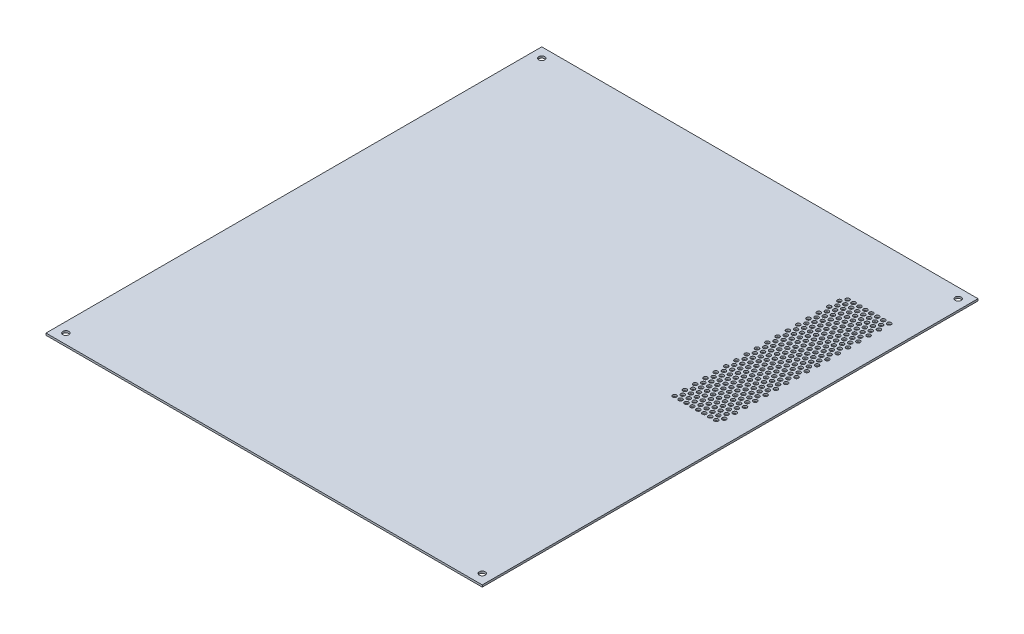
SolidWorks part; units mm, degrees
ref_plane "Front Plane" through (0, 0, 0) normal (0, 0, 1) x (1, 0, 0)
ref_plane "Top Plane" through (0, 0, 0) normal (0, 1, 0) x (1, 0, 0)
ref_plane "Right Plane" through (0, 0, 0) normal (1, 0, 0) x (0, 0, -1)
sketch "Sketch1" plane through (0, 0, 0) normal (0, 1, 0) x (1, 0, 0)
  line L0 (20, 20) -> (20, 480) construction
  line L1 (0, 0) -> (440, 0)
  line L2 (0, 0) -> (0, 500)
  line L3 (0, 500) -> (440, 500)
  line L4 (440, 0) -> (440, 500)
  line L5 (20, 480) -> (420, 480) construction
  line L6 (420, 20) -> (420, 480) construction
  line L7 (20, 20) -> (420, 20) construction
  line L9 (420, 440) -> (370, 440) construction
  line L10 (420, 440) -> (420, 260) construction
  line L11 (420, 260) -> (370, 260) construction
  line L12 (370, 440) -> (370, 260) construction
  circle A0 centre (372, 262) radius 2
  circle A1 centre (375, 267.1962) radius 2
  circle A2 centre (381, 267.1962) radius 2
  circle A3 centre (378, 262) radius 2
  circle A4 centre (387, 267.1962) radius 2
  circle A5 centre (384, 262) radius 2
  circle A6 centre (393, 267.1962) radius 2
  circle A7 centre (390, 262) radius 2
  circle A8 centre (399, 267.1962) radius 2
  circle A9 centre (396, 262) radius 2
  circle A10 centre (405, 267.1962) radius 2
  circle A11 centre (402, 262) radius 2
  circle A12 centre (411, 267.1962) radius 2
  circle A13 centre (408, 262) radius 2
  circle A14 centre (417, 267.1962) radius 2
  circle A15 centre (414, 262) radius 2
  circle A16 centre (381, 277.5862) radius 2
  circle A17 centre (378, 272.39) radius 2
  circle A18 centre (387, 277.5862) radius 2
  circle A19 centre (384, 272.39) radius 2
  circle A20 centre (393, 277.5862) radius 2
  circle A21 centre (390, 272.39) radius 2
  circle A22 centre (399, 277.5862) radius 2
  circle A23 centre (396, 272.39) radius 2
  circle A24 centre (405, 277.5862) radius 2
  circle A25 centre (402, 272.39) radius 2
  circle A26 centre (411, 277.5862) radius 2
  circle A27 centre (408, 272.39) radius 2
  circle A28 centre (417, 277.5862) radius 2
  circle A29 centre (414, 272.39) radius 2
  circle A30 centre (381, 287.9762) radius 2
  circle A31 centre (378, 282.78) radius 2
  circle A32 centre (387, 287.9762) radius 2
  circle A33 centre (384, 282.78) radius 2
  circle A34 centre (393, 287.9762) radius 2
  circle A35 centre (390, 282.78) radius 2
  circle A36 centre (399, 287.9762) radius 2
  circle A37 centre (396, 282.78) radius 2
  circle A38 centre (405, 287.9762) radius 2
  circle A39 centre (402, 282.78) radius 2
  circle A40 centre (411, 287.9762) radius 2
  circle A41 centre (408, 282.78) radius 2
  circle A42 centre (417, 287.9762) radius 2
  circle A43 centre (414, 282.78) radius 2
  circle A44 centre (381, 298.3662) radius 2
  circle A45 centre (378, 293.17) radius 2
  circle A46 centre (387, 298.3662) radius 2
  circle A47 centre (384, 293.17) radius 2
  circle A48 centre (393, 298.3662) radius 2
  circle A49 centre (390, 293.17) radius 2
  circle A50 centre (399, 298.3662) radius 2
  circle A51 centre (396, 293.17) radius 2
  circle A52 centre (405, 298.3662) radius 2
  circle A53 centre (402, 293.17) radius 2
  circle A54 centre (411, 298.3662) radius 2
  circle A55 centre (408, 293.17) radius 2
  circle A56 centre (417, 298.3662) radius 2
  circle A57 centre (414, 293.17) radius 2
  circle A58 centre (381, 308.7562) radius 2
  circle A59 centre (378, 303.56) radius 2
  circle A60 centre (387, 308.7562) radius 2
  circle A61 centre (384, 303.56) radius 2
  circle A62 centre (393, 308.7562) radius 2
  circle A63 centre (390, 303.56) radius 2
  circle A64 centre (399, 308.7562) radius 2
  circle A65 centre (396, 303.56) radius 2
  circle A66 centre (405, 308.7562) radius 2
  circle A67 centre (402, 303.56) radius 2
  circle A68 centre (411, 308.7562) radius 2
  circle A69 centre (408, 303.56) radius 2
  circle A70 centre (417, 308.7562) radius 2
  circle A71 centre (414, 303.56) radius 2
  circle A72 centre (381, 319.1462) radius 2
  circle A73 centre (378, 313.95) radius 2
  circle A74 centre (387, 319.1462) radius 2
  circle A75 centre (384, 313.95) radius 2
  circle A76 centre (393, 319.1462) radius 2
  circle A77 centre (390, 313.95) radius 2
  circle A78 centre (399, 319.1462) radius 2
  circle A79 centre (396, 313.95) radius 2
  circle A80 centre (405, 319.1462) radius 2
  circle A81 centre (402, 313.95) radius 2
  circle A82 centre (411, 319.1462) radius 2
  circle A83 centre (408, 313.95) radius 2
  circle A84 centre (417, 319.1462) radius 2
  circle A85 centre (414, 313.95) radius 2
  circle A86 centre (381, 329.5362) radius 2
  circle A87 centre (378, 324.34) radius 2
  circle A88 centre (387, 329.5362) radius 2
  circle A89 centre (384, 324.34) radius 2
  circle A90 centre (393, 329.5362) radius 2
  circle A91 centre (390, 324.34) radius 2
  circle A92 centre (399, 329.5362) radius 2
  circle A93 centre (396, 324.34) radius 2
  circle A94 centre (405, 329.5362) radius 2
  circle A95 centre (402, 324.34) radius 2
  circle A96 centre (411, 329.5362) radius 2
  circle A97 centre (408, 324.34) radius 2
  circle A98 centre (417, 329.5362) radius 2
  circle A99 centre (414, 324.34) radius 2
  circle A100 centre (381, 339.9262) radius 2
  circle A101 centre (378, 334.73) radius 2
  circle A102 centre (387, 339.9262) radius 2
  circle A103 centre (384, 334.73) radius 2
  circle A104 centre (393, 339.9262) radius 2
  circle A105 centre (390, 334.73) radius 2
  circle A106 centre (399, 339.9262) radius 2
  circle A107 centre (396, 334.73) radius 2
  circle A108 centre (405, 339.9262) radius 2
  circle A109 centre (402, 334.73) radius 2
  circle A110 centre (411, 339.9262) radius 2
  circle A111 centre (408, 334.73) radius 2
  circle A112 centre (417, 339.9262) radius 2
  circle A113 centre (414, 334.73) radius 2
  circle A114 centre (381, 350.3162) radius 2
  circle A115 centre (378, 345.12) radius 2
  circle A116 centre (387, 350.3162) radius 2
  circle A117 centre (384, 345.12) radius 2
  circle A118 centre (393, 350.3162) radius 2
  circle A119 centre (390, 345.12) radius 2
  circle A120 centre (399, 350.3162) radius 2
  circle A121 centre (396, 345.12) radius 2
  circle A122 centre (405, 350.3162) radius 2
  circle A123 centre (402, 345.12) radius 2
  circle A124 centre (411, 350.3162) radius 2
  circle A125 centre (408, 345.12) radius 2
  circle A126 centre (417, 350.3162) radius 2
  circle A127 centre (414, 345.12) radius 2
  circle A128 centre (381, 360.7062) radius 2
  circle A129 centre (378, 355.51) radius 2
  circle A130 centre (387, 360.7062) radius 2
  circle A131 centre (384, 355.51) radius 2
  circle A132 centre (393, 360.7062) radius 2
  circle A133 centre (390, 355.51) radius 2
  circle A134 centre (399, 360.7062) radius 2
  circle A135 centre (396, 355.51) radius 2
  circle A136 centre (405, 360.7062) radius 2
  circle A137 centre (402, 355.51) radius 2
  circle A138 centre (411, 360.7062) radius 2
  circle A139 centre (408, 355.51) radius 2
  circle A140 centre (417, 360.7062) radius 2
  circle A141 centre (414, 355.51) radius 2
  circle A142 centre (381, 371.0962) radius 2
  circle A143 centre (378, 365.9) radius 2
  circle A144 centre (387, 371.0962) radius 2
  circle A145 centre (384, 365.9) radius 2
  circle A146 centre (393, 371.0962) radius 2
  circle A147 centre (390, 365.9) radius 2
  circle A148 centre (399, 371.0962) radius 2
  circle A149 centre (396, 365.9) radius 2
  circle A150 centre (405, 371.0962) radius 2
  circle A151 centre (402, 365.9) radius 2
  circle A152 centre (411, 371.0962) radius 2
  circle A153 centre (408, 365.9) radius 2
  circle A154 centre (417, 371.0962) radius 2
  circle A155 centre (414, 365.9) radius 2
  circle A156 centre (381, 381.4862) radius 2
  circle A157 centre (378, 376.29) radius 2
  circle A158 centre (387, 381.4862) radius 2
  circle A159 centre (384, 376.29) radius 2
  circle A160 centre (393, 381.4862) radius 2
  circle A161 centre (390, 376.29) radius 2
  circle A162 centre (399, 381.4862) radius 2
  circle A163 centre (396, 376.29) radius 2
  circle A164 centre (405, 381.4862) radius 2
  circle A165 centre (402, 376.29) radius 2
  circle A166 centre (411, 381.4862) radius 2
  circle A167 centre (408, 376.29) radius 2
  circle A168 centre (417, 381.4862) radius 2
  circle A169 centre (414, 376.29) radius 2
  circle A170 centre (381, 391.8762) radius 2
  circle A171 centre (378, 386.68) radius 2
  circle A172 centre (387, 391.8762) radius 2
  circle A173 centre (384, 386.68) radius 2
  circle A174 centre (393, 391.8762) radius 2
  circle A175 centre (390, 386.68) radius 2
  circle A176 centre (399, 391.8762) radius 2
  circle A177 centre (396, 386.68) radius 2
  circle A178 centre (405, 391.8762) radius 2
  circle A179 centre (402, 386.68) radius 2
  circle A180 centre (411, 391.8762) radius 2
  circle A181 centre (408, 386.68) radius 2
  circle A182 centre (417, 391.8762) radius 2
  circle A183 centre (414, 386.68) radius 2
  circle A184 centre (381, 402.2662) radius 2
  circle A185 centre (378, 397.07) radius 2
  circle A186 centre (387, 402.2662) radius 2
  circle A187 centre (384, 397.07) radius 2
  circle A188 centre (393, 402.2662) radius 2
  circle A189 centre (390, 397.07) radius 2
  circle A190 centre (399, 402.2662) radius 2
  circle A191 centre (396, 397.07) radius 2
  circle A192 centre (405, 402.2662) radius 2
  circle A193 centre (402, 397.07) radius 2
  circle A194 centre (411, 402.2662) radius 2
  circle A195 centre (408, 397.07) radius 2
  circle A196 centre (417, 402.2662) radius 2
  circle A197 centre (414, 397.07) radius 2
  circle A198 centre (381, 412.6562) radius 2
  circle A199 centre (378, 407.46) radius 2
  circle A200 centre (387, 412.6562) radius 2
  circle A201 centre (384, 407.46) radius 2
  circle A202 centre (393, 412.6562) radius 2
  circle A203 centre (390, 407.46) radius 2
  circle A204 centre (399, 412.6562) radius 2
  circle A205 centre (396, 407.46) radius 2
  circle A206 centre (405, 412.6562) radius 2
  circle A207 centre (402, 407.46) radius 2
  circle A208 centre (411, 412.6562) radius 2
  circle A209 centre (408, 407.46) radius 2
  circle A210 centre (417, 412.6562) radius 2
  circle A211 centre (414, 407.46) radius 2
  circle A212 centre (381, 423.0462) radius 2
  circle A213 centre (378, 417.85) radius 2
  circle A214 centre (387, 423.0462) radius 2
  circle A215 centre (384, 417.85) radius 2
  circle A216 centre (393, 423.0462) radius 2
  circle A217 centre (390, 417.85) radius 2
  circle A218 centre (399, 423.0462) radius 2
  circle A219 centre (396, 417.85) radius 2
  circle A220 centre (405, 423.0462) radius 2
  circle A221 centre (402, 417.85) radius 2
  circle A222 centre (411, 423.0462) radius 2
  circle A223 centre (408, 417.85) radius 2
  circle A224 centre (417, 423.0462) radius 2
  circle A225 centre (414, 417.85) radius 2
  circle A226 centre (381, 433.4362) radius 2
  circle A227 centre (378, 428.24) radius 2
  circle A228 centre (387, 433.4362) radius 2
  circle A229 centre (384, 428.24) radius 2
  circle A230 centre (393, 433.4362) radius 2
  circle A231 centre (390, 428.24) radius 2
  circle A232 centre (399, 433.4362) radius 2
  circle A233 centre (396, 428.24) radius 2
  circle A234 centre (405, 433.4362) radius 2
  circle A235 centre (402, 428.24) radius 2
  circle A236 centre (411, 433.4362) radius 2
  circle A237 centre (408, 428.24) radius 2
  circle A238 centre (417, 433.4362) radius 2
  circle A239 centre (414, 428.24) radius 2
  circle A240 centre (375, 277.5862) radius 2
  circle A241 centre (372, 272.39) radius 2
  circle A242 centre (375, 287.9762) radius 2
  circle A243 centre (372, 282.78) radius 2
  circle A244 centre (375, 298.3662) radius 2
  circle A245 centre (372, 293.17) radius 2
  circle A246 centre (375, 308.7562) radius 2
  circle A247 centre (372, 303.56) radius 2
  circle A248 centre (375, 319.1462) radius 2
  circle A249 centre (372, 313.95) radius 2
  circle A250 centre (375, 329.5362) radius 2
  circle A251 centre (372, 324.34) radius 2
  circle A252 centre (375, 339.9262) radius 2
  circle A253 centre (372, 334.73) radius 2
  circle A254 centre (375, 350.3162) radius 2
  circle A255 centre (372, 345.12) radius 2
  circle A256 centre (375, 360.7062) radius 2
  circle A257 centre (372, 355.51) radius 2
  circle A258 centre (375, 371.0962) radius 2
  circle A259 centre (372, 365.9) radius 2
  circle A260 centre (375, 381.4862) radius 2
  circle A261 centre (372, 376.29) radius 2
  circle A262 centre (375, 391.8762) radius 2
  circle A263 centre (372, 386.68) radius 2
  circle A264 centre (375, 402.2662) radius 2
  circle A265 centre (372, 397.07) radius 2
  circle A266 centre (375, 412.6562) radius 2
  circle A267 centre (372, 407.46) radius 2
  circle A268 centre (375, 423.0462) radius 2
  circle A269 centre (372, 417.85) radius 2
  circle A270 centre (375, 433.4362) radius 2
  circle A271 centre (372, 428.24) radius 2
  circle A272 centre (10, 490) radius 3
  circle A273 centre (430, 490) radius 3
  circle A274 centre (430, 10) radius 3
  circle A275 centre (10, 10) radius 3
  point P566 (11.815, 500)
  point P567 (13.0841, 0)
  dimension "D7" = 2
  dimension "D8" = 2
  dimension "D12" = 10
  dimension "D14" = 10
  dimension "D21" = 6
  dimension "D22" = 4
  dimension "D2" = 180
  dimension "D3" = 50
  dimension "D4" = 60
  dimension "D5" = 500
  dimension "D6" = 440
  dimension "D9" = 8
  dimension "D10" = 17
  dimension "D11" = 6
  dimension "D13" = 5.1962
  dimension "D15" = 10
  dimension "D16" = 10
  dimension "D17" = 10
  dimension "D18" = 10
  dimension "D19" = 10
  dimension "D20" = 10
  dimension "D1" = 20
extrude "Boss-Extrude1" add sketch "Sketch1" along normal blind 2
